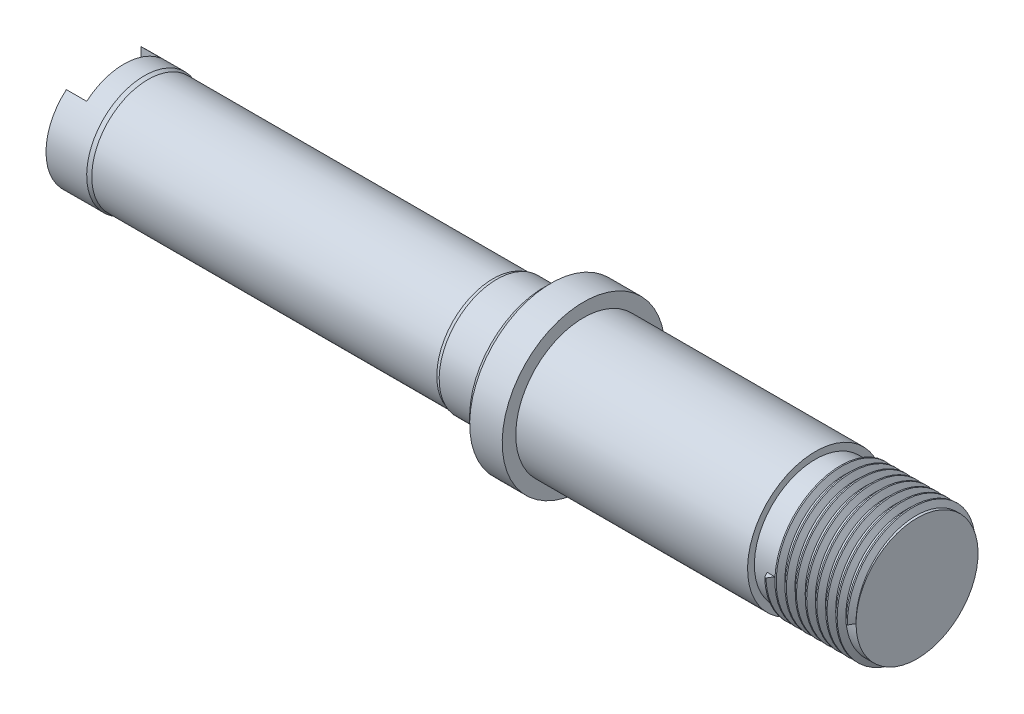
SolidWorks part; units mm, degrees
material "201 Annealed Stainless Steel (SS)"
ref_plane "Front Plane" through (0, 0, 0) normal (0, 0, 1) x (1, 0, 0)
ref_plane "Top Plane" through (0, 0, 0) normal (0, 1, 0) x (1, 0, 0)
ref_plane "Right Plane" through (0, 0, 0) normal (1, 0, 0) x (0, 0, -1)
sketch "Sketch1" plane through (0, 0, 0) normal (0, 0, 1) x (1, 0, 0)
  line L0 (32, 0) -> (175.1014, 0) construction
  line L1 (0, 5) -> (0, 8.5)
  line L2 (0, 8.5) -> (6, 8.5)
  line L3 (6, 8.5) -> (6.55, 8.3)
  line L4 (6.55, 8.3) -> (57.45, 8.3)
  line L5 (57.45, 8.3) -> (58, 8.5)
  line L6 (58, 8.5) -> (65, 8.5)
  line L7 (65, 8.5) -> (65, 11)
  line L8 (65, 11) -> (66, 12)
  line L9 (66, 12) -> (70.8, 12)
  line L10 (70.8, 12) -> (70.8, 10)
  line L11 (70.8, 10) -> (105, 10)
  line L12 (105, 10) -> (105, 9)
  line L13 (105, 9) -> (108, 9)
  line L14 (108, 9) -> (120, 9)
  line L15 (87.4589, 10) -> (93.3279, 10)
  line L17 (120, 9) -> (120, 0)
  line L19 (120, 0) -> (32, 0)
  line L20 (0, 5) -> (27, 5)
  line L21 (27, 5) -> (32, 0)
  point P3 (106.5, 9)
  point P25 (65, 9.75)
  dimension "D2" = 6
  dimension "D3" = 6.55
  dimension "D4" = 8.3
  dimension "D5" = 57.45
  dimension "D6" = 58
  dimension "D7" = 8.5
  dimension "D8" = 65
  dimension "D9" = 66
  dimension "D10" = 12
  dimension "D11" = 11
  dimension "D12" = 70.8
  dimension "D13" = 8.3
  dimension "D14" = 9
  dimension "D15" = 10
  dimension "D16" = 120
  dimension "D17" = 105
  dimension "D18" = 108
  dimension "D19" = 12
  dimension "D20" = 27
  dimension "D21" = 135
  dimension "D22" = 5
revolve "Revolve1" add sketch "Sketch1" angle 360 about L0 region at (69.5025, 4.9241, 0)
thread "Thread1" pitch 1.5 method extrude profile "Thread Profile6" start angle 0, offset 0, length 12, pitch 1.5, diameter 18
ref_plane "Plane6" through (120, 0, 9) normal (0, -1, 0) x (0, 0, 1)
sketch "Thread Profile6" plane through (120, 0, 9) normal (0, -1, 0) x (0, 0, 1)
  line L0 (0, 0) -> (0, 1.5) construction
  line L1 (0, 0) -> (0.8119, 0.4687)
  line L2 (0.8119, 0.4687) -> (0.8119, 0.6562)
  line L3 (0.8119, 0.6562) -> (0, 1.125)
  line L4 (0.8119, 0.5625) -> (0, 0.5625) construction
  line L11 (0, 0) -> (0, 1.125)
  point P2 (0, 0)
  dimension "Pitch" = 1.5
  dimension "Profile_Angle" = 60
  dimension "Profile_Land" = 0.1875
  dimension "Profile_Height" = 0.8119
thread "Thread2" pitch 1.5 method cut profile "Thread Profile7" start angle 0, offset 2, length 19, pitch 1.5, diameter 10
ref_plane "Plane7" through (-2, 0, -5) normal (0, -1, 0) x (0, 0, -1)
sketch "Thread Profile7" plane through (-2, 0, -5) normal (0, -1, 0) x (0, 0, -1)
  line L0 (0, 0) -> (0, 1.5) construction
  line L1 (0, 0) -> (0.8119, 0.4687)
  line L2 (0.8119, 0.4687) -> (0.8119, 0.6562)
  line L3 (0.8119, 0.6562) -> (0, 1.125)
  line L4 (0.8119, 0.5625) -> (0, 0.5625) construction
  line L11 (0, 0) -> (0, 1.125)
  point P2 (0, 0)
  dimension "Pitch" = 1.5
  dimension "Profile_Angle" = 60
  dimension "Profile_Land" = 0.1875
  dimension "Profile_Height" = 0.8119
sketch "Sketch29" plane through (0, 0, 0) normal (0, 1, 0) x (1, 0, 0)
  line L4 (0, 0) -> (9.9871, 0) construction
  line L5 (3, 5.5) -> (0, 5.5)
  line L6 (3, 5.5) -> (3, -5.5)
  line L7 (0, 5.5) -> (0, -5.5)
  line L8 (3, -5.5) -> (0, -5.5)
  line L9 (3, 5.5) -> (0, -5.5) construction
  line L10 (0, 5.5) -> (3, -5.5) construction
  point P3 (1.5, 0)
  dimension "D1" = 3
  dimension "D2" = 5.5
  dimension "D3" = 5.5
extrude "Cut-Extrude1" cut sketch "Sketch29" against normal mid plane 20
